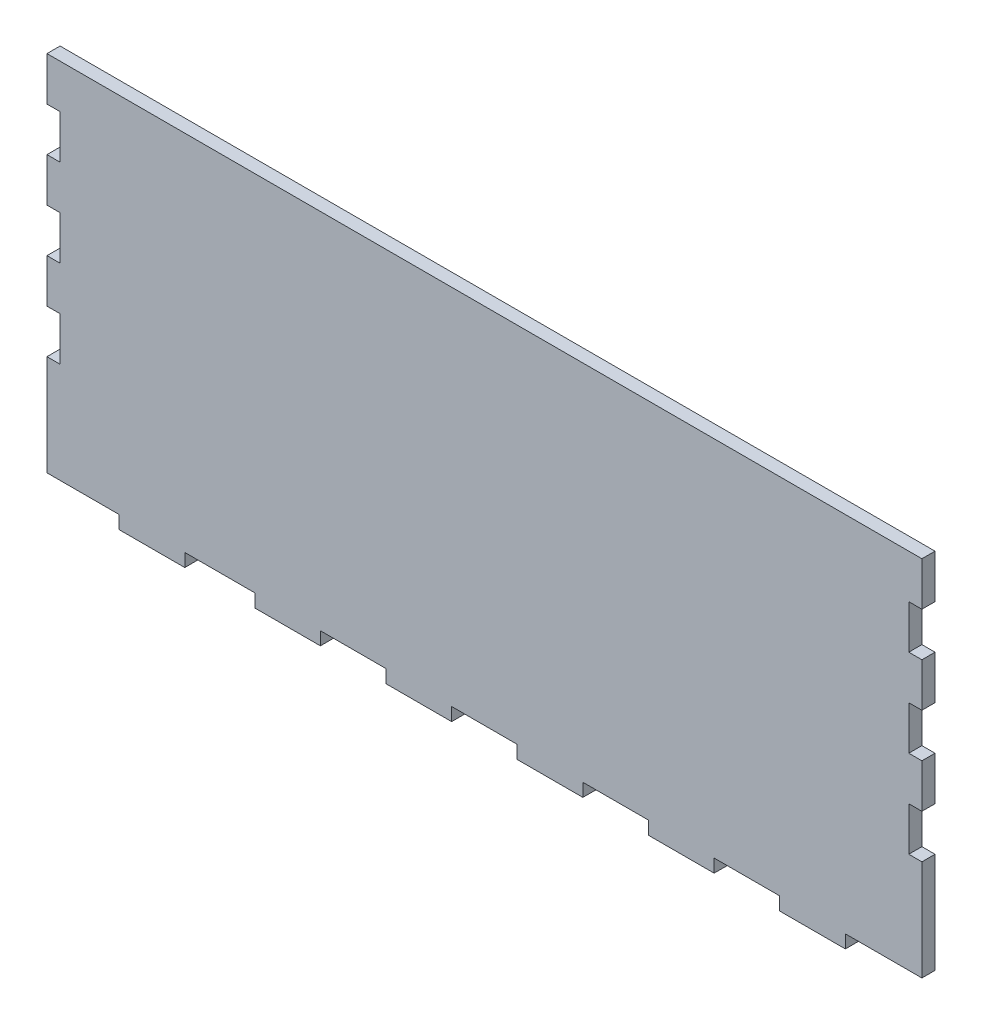
SolidWorks part; units mm, degrees
ref_plane "Front Plane" through (0, 0, 0) normal (0, 0, 1) x (1, 0, 0)
ref_plane "Top Plane" through (0, 0, 0) normal (0, 1, 0) x (1, 0, 0)
ref_plane "Right Plane" through (0, 0, 0) normal (1, 0, 0) x (0, 0, -1)
sketch "Sketch1" plane through (0, 0, 0) normal (0, 0, 1) x (1, 0, 0)
  line L0 (-97, 0) -> (97, 0) construction
  line L1 (0, -25.5) -> (0, 57.5) construction
  line L2 (100, -2.5) -> (97, -2.5)
  line L3 (-97, 57.5) -> (97, 57.5)
  line L4 (100, -25.5) -> (100, -2.5)
  line L5 (0, -25.5) -> (7.5, -25.5)
  line L6 (-97, -25.5) -> (-100, -25.5)
  line L7 (-100, -25.5) -> (-100, -2.5)
  line L8 (-97, 57.5) -> (-100, 57.5)
  line L9 (-100, 57.5) -> (-100, 47.5)
  line L10 (-100, 47.5) -> (-97, 47.5)
  line L11 (-97, 47.5) -> (-97, 37.5)
  line L12 (-97, 37.5) -> (-100, 37.5)
  line L13 (-100, 37.5) -> (-100, 27.5)
  line L14 (100, 17.5) -> (100, 7.5)
  line L15 (-100, 27.5) -> (-97, 27.5)
  line L16 (-97, 27.5) -> (-97, 17.5)
  line L17 (97, 7.5) -> (100, 7.5)
  line L18 (97, 17.5) -> (100, 17.5)
  line L19 (97, 7.5) -> (97, -2.5)
  line L20 (97, 27.5) -> (97, 17.5)
  line L21 (100, 27.5) -> (97, 27.5)
  line L22 (100, 37.5) -> (100, 27.5)
  line L23 (97, 37.5) -> (100, 37.5)
  line L24 (97, 47.5) -> (97, 37.5)
  line L25 (100, 47.5) -> (97, 47.5)
  line L26 (100, 57.5) -> (100, 47.5)
  line L27 (97, 57.5) -> (100, 57.5)
  line L28 (7.5, -25.5) -> (7.5, -28.5)
  line L29 (7.5, -28.5) -> (22.5, -28.5)
  line L30 (22.5, -28.5) -> (22.5, -25.5)
  line L31 (30, -25.5) -> (37.5, -25.5)
  line L32 (37.5, -25.5) -> (37.5, -28.5)
  line L33 (37.5, -28.5) -> (52.5, -28.5)
  line L34 (52.5, -28.5) -> (52.5, -25.5)
  line L35 (60, -25.5) -> (67.5, -25.5)
  line L36 (67.5, -25.5) -> (67.5, -28.5)
  line L37 (67.5, -28.5) -> (82.5, -28.5)
  line L38 (82.5, -28.5) -> (82.5, -25.5)
  line L39 (22.5, -25.5) -> (30, -25.5)
  line L40 (52.5, -25.5) -> (60, -25.5)
  line L41 (82.5, -25.5) -> (97, -25.5)
  line L42 (0, -25.5) -> (-7.5, -25.5)
  line L43 (-7.5, -25.5) -> (-7.5, -28.5)
  line L44 (-7.5, -28.5) -> (-22.5, -28.5)
  line L45 (-22.5, -28.5) -> (-22.5, -25.5)
  line L46 (-22.5, -25.5) -> (-37.5, -25.5)
  line L47 (-37.5, -25.5) -> (-37.5, -28.5)
  line L48 (-37.5, -28.5) -> (-52.5, -28.5)
  line L49 (-52.5, -28.5) -> (-52.5, -25.5)
  line L50 (-52.5, -25.5) -> (-68.5, -25.5)
  line L51 (-68.5, -25.5) -> (-68.5, -28.5)
  line L52 (-100, -2.5) -> (-97, -2.5)
  line L53 (97, -25.5) -> (100, -25.5)
  line L56 (-97, 7.5) -> (-97, -2.5)
  line L57 (-97, 17.5) -> (-100, 17.5)
  line L58 (-97, 7.5) -> (-100, 7.5)
  line L59 (-100, 17.5) -> (-100, 7.5)
  line L60 (-68.5, -28.5) -> (-83.5, -28.5)
  line L62 (-83.5, -28.5) -> (-83.5, -25.5)
  line L63 (-83.5, -25.5) -> (-97, -25.5)
  dimension "D2" = 7.5
  dimension "D4" = 83
  dimension "D5" = 10
  dimension "D6" = 194
  dimension "D8" = 7.5
  dimension "D9" = 15
  dimension "D10" = 3
  dimension "D11" = 10
  dimension "D7" = 10
  dimension "D13" = 10
  dimension "D12" = 10
  dimension "D14" = 7.5
  dimension "D15" = 14.5
  dimension "D16" = 10
  dimension "D18" = 3
  dimension "D19" = 15
  dimension "D20" = 15
  dimension "D21" = 15
  dimension "D22" = 16
  dimension "D23" = 15
extrude "Boss-Extrude1" add sketch "Sketch1" along normal blind 3
